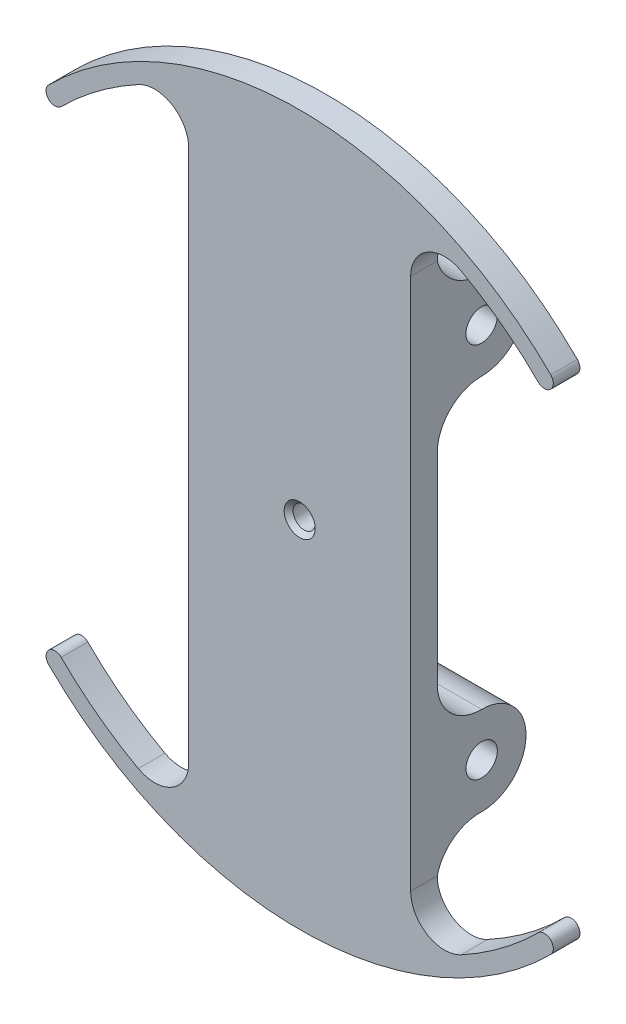
SolidWorks part; units mm, degrees
ref_plane "Front Plane" through (0, 0, 0) normal (0, 0, 1) x (1, 0, 0)
ref_plane "Top Plane" through (0, 0, 0) normal (0, 1, 0) x (1, 0, 0)
ref_plane "Right Plane" through (0, 0, 0) normal (1, 0, 0) x (0, 0, -1)
sketch "Sketch3" plane through (0, 0, 0) normal (0, 0, 1) x (1, 0, 0)
  line L0 (-35.921, -35.921) -> (-34.125, -34.125) construction
  line L1 (-15.875, -38.1) -> (0, -38.1) construction
  line L2 (-15.875, -38.1) -> (-15.875, 38.1)
  line L3 (-15.875, 38.1) -> (0, 38.1) construction
  line L4 (15.875, -38.1) -> (15.875, 38.1)
  line L5 (-15.875, -38.1) -> (15.875, 38.1) construction
  line L6 (-15.875, 38.1) -> (15.875, -38.1) construction
  line L7 (35.921, -35.921) -> (34.125, -34.125) construction
  line L8 (0, -50.8) -> (0, 50.8) construction
  line L9 (0, 38.1) -> (15.875, 38.1) construction
  line L10 (0, -38.1) -> (15.875, -38.1) construction
  line L11 (-34.125, -34.125) -> (-15.875, -15.875) construction
  line L12 (34.125, 34.125) -> (35.921, 35.921) construction
  line L13 (-15.875, -15.875) -> (0, 0) construction
  line L14 (15.875, -15.875) -> (0, 0) construction
  line L15 (-34.125, 34.125) -> (-35.921, 35.921) construction
  line L16 (34.125, -34.125) -> (15.875, -15.875) construction
  line L17 (0, 0) -> (-15.875, 15.875) construction
  line L18 (0, 0) -> (15.875, 15.875) construction
  line L19 (-15.875, 15.875) -> (-34.125, 34.125) construction
  line L20 (15.875, 15.875) -> (34.125, 34.125) construction
  arc A0 (-35.921, -35.921) -> (35.921, -35.921) centre (0, 0) ccw
  arc A1 (-34.125, -34.125) -> (-23.0827, -42.3818) centre (0, 0) ccw
  arc A2 (-15.875, 38.1) -> (-23.0827, 42.3818) centre (-20.7507, 38.1) ccw
  arc A3 (15.875, 38.1) -> (23.0827, 42.3818) centre (20.7507, 38.1) cw
  arc A4 (-15.875, -38.1) -> (-23.0827, -42.3818) centre (-20.7507, -38.1) cw
  arc A5 (15.875, -38.1) -> (23.0827, -42.3818) centre (20.7507, -38.1) ccw
  arc A6 (-35.921, 35.921) -> (-35.921, -35.921) centre (0, 0) ccw construction
  circle A7 centre (0, 0) radius 50.8 construction
  arc A8 (-34.125, 34.125) -> (-34.125, -34.125) centre (0, 0) ccw construction
  circle A9 centre (0, 0) radius 48.26 construction
  arc A10 (34.125, -34.125) -> (34.125, 34.125) centre (0, 0) ccw construction
  arc A11 (34.125, 34.125) -> (23.0827, 42.3818) centre (0, 0) ccw
  arc A12 (35.921, -35.921) -> (35.921, 35.921) centre (0, 0) ccw construction
  arc A13 (35.921, 35.921) -> (-35.921, 35.921) centre (0, 0) ccw
  arc A14 (0, 48.26) -> (-23.0827, 42.3818) centre (0, 0) ccw construction
  arc A15 (-23.0827, 42.3818) -> (-34.125, 34.125) centre (0, 0) ccw
  arc A16 (23.0827, 42.3818) -> (0, 48.26) centre (0, 0) ccw construction
  arc A17 (-23.0827, -42.3818) -> (0, -48.26) centre (0, 0) ccw construction
  arc A18 (23.0827, -42.3818) -> (34.125, -34.125) centre (0, 0) ccw
  arc A19 (0, -48.26) -> (23.0827, -42.3818) centre (0, 0) ccw construction
  arc A20 (-35.921, 35.921) -> (-34.125, 34.125) centre (-35.023, 35.023) ccw
  arc A21 (34.125, 34.125) -> (35.921, 35.921) centre (35.023, 35.023) ccw
  arc A22 (-35.921, -35.921) -> (-34.125, -34.125) centre (-35.023, -35.023) cw
  arc A23 (34.125, -34.125) -> (35.921, -35.921) centre (35.023, -35.023) cw
  point P0 (0, 0)
  point P13 (0, 0)
  point P16 (0, 0)
  point P18 (0, 0)
  dimension "D3" = 2.54
  dimension "D6" = 101.6
  dimension "D1" = 76.2
  dimension "D2" = 31.75
  dimension "D4" = 45
  dimension "D5" = 45
extrude "Boss-Extrude2" add sketch "Sketch3" along normal blind 3.81
sketch "Sketch5" plane through (15.875, 0, 0) normal (1, 0, 0) x (0, 0, -1)
  line L0 (0, 26.9938) -> (0, -26.9938)
  line L1 (0, -38.1) -> (0, 38.1) construction
  line L2 (0, 26.9938) -> (6.35, 26.9939) construction
  line L3 (6.35, 26.9939) -> (6.35, -26.9938) construction
  line L4 (6.35, -26.9938) -> (0, -26.9938) construction
  line L5 (0, 38.1) -> (0, 14.2939)
  line L6 (0, -14.2939) -> (0, -38.1)
  circle A0 centre (-0.0451, 26.9938) radius 0.0451
  arc A2 (6.35, 20.6439) -> (6.3413, 33.3438) centre (6.35, 26.9939) ccw
  arc A3 (6.0778, -33.338) -> (6.2617, -20.6445) centre (6.35, -26.9938) ccw
  arc A4 (6.35, 20.6439) -> (0, 14.2939) centre (6.3675, 14.2763) ccw
  arc A5 (6.3413, 33.3438) -> (0, 38.1) centre (6.1542, 39.6999) cw
  arc A6 (6.35, -20.6438) -> (0, -14.2939) centre (6.2623, -14.3815) cw
  arc A7 (6.35, -33.3439) -> (0, -38.1) centre (6.0797, -39.6) ccw
  arc A8 (6.3413, 33.3438) -> (0, 26.9938) centre (6.35, 26.9939) ccw construction
  arc A9 (0, 26.9938) -> (6.35, 20.6439) centre (6.35, 26.9939) ccw construction
  arc A10 (6.2617, -20.6445) -> (0, -26.9938) centre (6.35, -26.9938) ccw construction
  arc A11 (0, -26.9938) -> (6.0778, -33.338) centre (6.35, -26.9938) ccw construction
  point P5 (0, 0)
  line M6 (0, -38.1) -> (0, 38.1)
  dimension "D1" = 53.9877
  dimension "D2" = 6.35
  dimension "D3" = 12.7
  dimension "D4" = 12.7
extrude "Boss-Extrude4" add sketch "Sketch5" against normal up to surface (31.75 mm away) contours A2 A5 L0 A4 M6 | A7 A3 A6 L6 M6 region at (15.875, 26.931, -5.3159) region at (15.875, -26.9385, -5.3244) up to face at (-15.875, 0, 1.905)
hole_wizard "#8 Clearance Hole1" positions "Sketch8" profile "Sketch7" hole size "#8" standard "ANSI Inch" end condition through all
sketch "Sketch8" plane through (15.875, 0, 0) normal (1, 0, 0) x (0, 0, -1)
  point P7 (6.35, 26.9939)
  point P10 (6.35, -26.8934)
  point P13 (0, 0)
  point P14 (0, 0)
sketch "Sketch7" plane through (15.875, 26.9939, -6.35) normal (0, 1, 0) x (0, 0, -1)
  line L0 (0, 0) -> (0, 52.168)
  line L1 (0, 52.168) -> (2.2479, 52.168)
  line L2 (2.2479, 52.168) -> (2.2479, 0)
  line L5 (2.2479, 0) -> (0, 0)
  line L11 (0, -6.35) -> (0, 107.95) construction
  dimension "Thru Hole Dia." = 4.4958
  dimension "Thru Hole Depth" = 52.168
hole_wizard "1/8 (0.125) Diameter Hole1" positions "Sketch9" profile "Sketch10" hole size "1/8" standard "ANSI Inch" end condition up to next
sketch "Sketch9" plane through (0, 0, 0) normal (0, 0, -1) x (-1, 0, 0)
  point P0 (0, 0)
sketch "Sketch10" plane through (0, 0, 0) normal (1, 0, 0) x (0, 1, 0)
  line L0 (0, 0) -> (0, 3.81)
  line L1 (0, 3.81) -> (2.2225, 3.81)
  line L2 (1.5875, 3.175) -> (1.5875, 0.635)
  line L3 (1.5875, 0.635) -> (2.2225, 0)
  line L5 (2.2225, 0) -> (0, 0)
  line L6 (-1.5875, 0.635) -> (-2.2225, 0) construction
  line L7 (2.2225, 3.81) -> (1.5875, 3.175)
  line L8 (-2.2225, 3.81) -> (-1.5875, 3.175) construction
  line L11 (0, -6.35) -> (0, 107.95) construction
  dimension "Thru Hole Dia." = 3.175
  dimension "Thru Hole Depth" = 3.81
  dimension "Near C'Sink Dia." = 4.445
  dimension "Near C'Sink Angle" = 90
  dimension "Far C'Sink Dia." = 4.445
  dimension "Far C'Sink Angle" = 90
